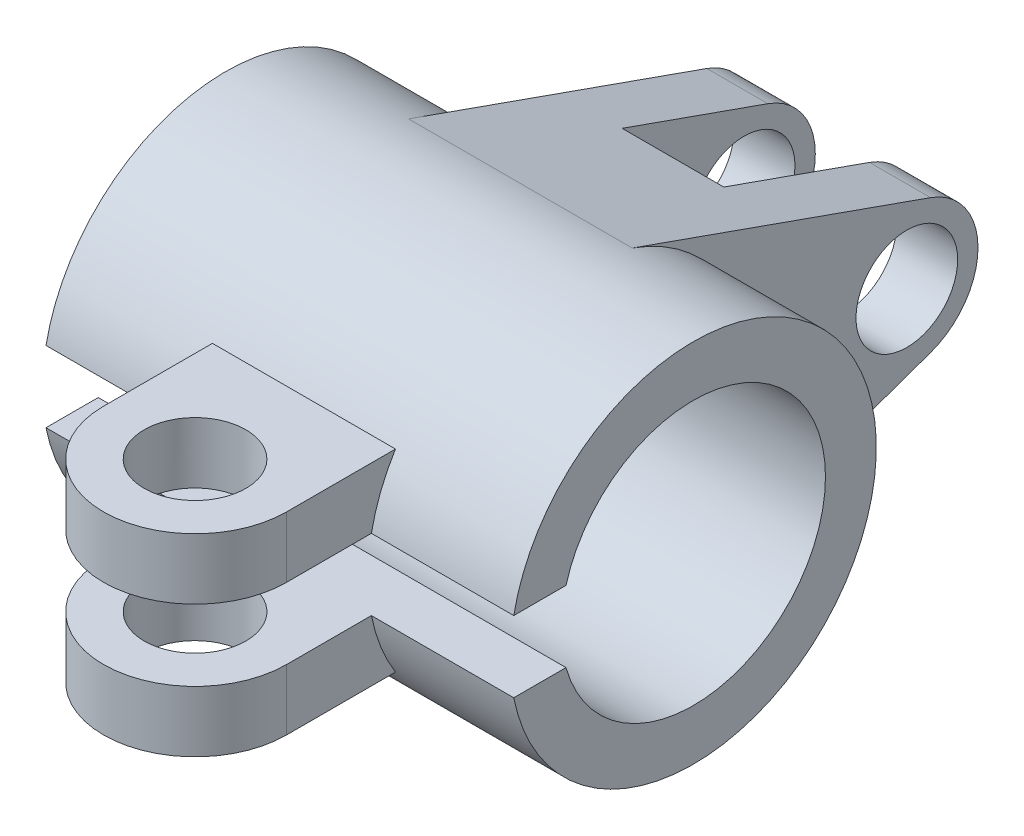
SolidWorks part; units mm, degrees
ref_plane "Front Plane" through (0, 0, 0) normal (0, 0, 1) x (1, 0, 0)
ref_plane "Top Plane" through (0, 0, 0) normal (0, 1, 0) x (1, 0, 0)
ref_plane "Right Plane" through (0, 0, 0) normal (1, 0, 0) x (0, 0, -1)
sketch "Sketch1" plane through (0, 0, 0) normal (1, 0, 0) x (0, 0, -1)
  line L0 (-12.52, 3.5) -> (-35, 3.5)
  line L1 (-35, 3.5) -> (-35, 9.5)
  line L2 (-35, 9.5) -> (-15.2889, 9.5)
  line L3 (-0.7612, 0) -> (-50000.7612, 0) construction
  line L4 (0, 0) -> (0, 50000) construction
  line L5 (-35, -9.5) -> (-15.2889, -9.5)
  line L6 (-35, -3.5) -> (-35, -9.5)
  line L7 (-12.52, -3.5) -> (-35, -3.5)
  line L8 (35.3333, 6.5997) -> (6, 16.9706)
  line L9 (35.3333, -6.5997) -> (6, -16.9706)
  line L10 (21, 11.6673) -> (21, -11.6673)
  circle A0 centre (0, 0) radius 13
  circle A1 centre (0, 0) radius 18
  circle A2 centre (33, 0) radius 5
  circle A3 centre (33, 0) radius 7
  dimension "D1" = 26
  dimension "D2" = 36
  dimension "D6" = 10
  dimension "D7" = 14
  dimension "D3" = 7
  dimension "D4" = 6
  dimension "D5" = 35
  dimension "D8" = 33
  dimension "D9" = 12
extrude "Boss-Extrude1" add sketch "Sketch1" along normal mid plane 46 contours A1 L0 A0 L7 region at (0, 4.0067, 15.0882)
extrude "Boss-Extrude3" add sketch "Sketch1<4>" along normal mid plane 22 contours A1 L9 L10 L8 region at (0, 13.9691, -13.3763)
sketch "Sketch1<4>" plane through (0, 0, 0) normal (1, 0, 0) x (0, 0, -1) same geometry as "Sketch1"
extrude "Boss-Extrude4" add sketch "Sketch1<5>" along normal blind 6 from offset 5 contours A3 L8 L10 L9 | A3 A2 region at (0, 0, -24.8369) region at (0, 3.9271, -38.5538)
sketch "Sketch1<5>" plane through (0, 0, 0) normal (1, 0, 0) x (0, 0, -1) same geometry as "Sketch1"
extrude "Boss-Extrude5" add sketch "Sketch1<6>" against normal blind 6 from offset 5 contours A3 L8 L10 L9 | A3 A2 region at (0, 0, -24.8369) region at (0, 3.9271, -38.5538) offset against normal yes
sketch "Sketch1<6>" plane through (0, 0, 0) normal (1, 0, 0) x (0, 0, -1) same geometry as "Sketch1"
extrude "Boss-Extrude6" add sketch "Sketch1<8>" along normal mid plane 18 contours A1 L2 L1 L0 | A1 L7 L6 L5 region at (0, 6.5641, 25.8281) region at (0, -6.5641, 25.8281)
sketch "Sketch1<8>" plane through (0, 0, 0) normal (1, 0, 0) x (0, 0, -1) same geometry as "Sketch1"
fillet "Fillet5" 2 edges at (9, 6.5, 35) (-9, 6.5, 35) type full round first side face at (9, 6.5267, 25.8041) second side face at (-9, 6.5267, 25.8041) middle face at (0, 6.5, 35)
fillet "Fillet6" 2 edges at (9, -6.5, 35) (-9, -6.5, 35) type full round first side face at (9, -6.5267, 25.8041) second side face at (-9, -6.5267, 25.8041) middle face at (0, -6.5, 35)
sketch "Sketch3" plane through (0, 9.5, 0) normal (0, 1, 0) x (1, 0, 0)
  circle A0 centre (0, -26) radius 5
  dimension "D1" = 10
extrude "Cut-Extrude1" cut sketch "Sketch3" against normal through all and the other way through all
